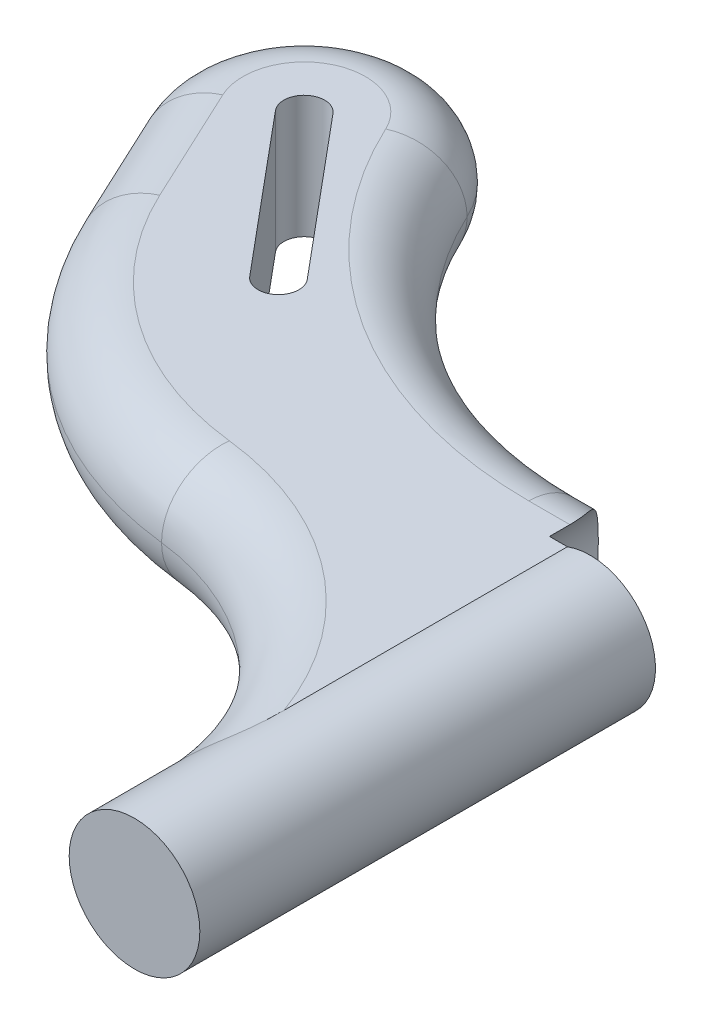
SolidWorks part; units mm, degrees
ref_plane "Front Plane" through (0, 0, 0) normal (0, 0, 1) x (1, 0, 0)
ref_plane "Top Plane" through (0, 0, 0) normal (0, 1, 0) x (1, 0, 0)
ref_plane "Right Plane" through (0, 0, 0) normal (1, 0, 0) x (0, 0, -1)
sketch "Sketch1" plane through (0, 0, 0) normal (0, 0, 1) x (1, 0, 0)
  circle A0 centre (0, 0) radius 8
  dimension "D1" = 16
extrude "Boss-Extrude1" add sketch "Sketch1" along normal blind 55.7812
sketch "Sketch2" plane through (0, 0, 0) normal (0, 1, 0) x (1, 0, 0)
  line L12 (0, 0) -> (0, -47.7812)
  line L13 (-71.8118, 9.1529) -> (-44.6353, 21.8588) construction
  line L14 (0, -47.7812) -> (-8, -47.7812)
  line L16 (-8, 0) -> (-8, -55.7812) construction
  line L17 (0, 0) -> (0, 10)
  line L22 (0, 10) -> (-10, 10)
  line L23 (-78.5882, 23.6471) -> (-71.8118, 9.1529)
  line L24 (-65, 30) -> (-65, 0) construction
  line L25 (-65, 0) -> (0, 0) construction
  line L26 (-51.4118, 36.3529) -> (0, -73.6111) construction
  line L28 (-8, -55.7812) -> (-8, -47.7812) construction
  line L30 (-65, 30) -> (-48.9689, 10.8166) construction
  line L32 (-66.9183, 28.3969) -> (-50.8872, 9.2135)
  line L35 (-47.0505, 12.4197) -> (-63.0817, 31.6031)
  line L36 (-48.9689, 10.8166) -> (0, -47.7812) construction
  arc A1 (-10, 10) -> (-51.4118, 36.3529) centre (-10, 55.7143) cw
  arc A3 (-51.4118, 36.3529) -> (-78.5882, 23.6471) centre (-65, 30) ccw
  arc A5 (-8, -47.7812) -> (-35.5631, -16.9075) centre (-39.0725, -47.7812) ccw
  arc A6 (-35.5631, -16.9075) -> (-71.8118, 9.1529) centre (-30.4, 28.5143) cw
  arc A7 (-63.0817, 31.6031) -> (-66.9183, 28.3969) centre (-65, 30) ccw
  arc A8 (-50.8872, 9.2135) -> (-47.0505, 12.4197) centre (-48.9689, 10.8166) ccw
  arc A9 (-50.572, 12.7349) -> (-50.8872, 9.2135) centre (-48.9689, 10.8166) ccw construction
  arc A10 (-63.3969, 28.0817) -> (-63.0817, 31.6031) centre (-65, 30) ccw construction
  arc A11 (-65, 27.5) -> (-63.3969, 28.0817) centre (-65, 30) ccw
  arc A12 (-66.9183, 28.3969) -> (-65, 27.5) centre (-65, 30) ccw construction
  arc A13 (-47.0505, 12.4197) -> (-50.572, 12.7349) centre (-48.9689, 10.8166) ccw construction
  point P21 (0, -45.9096)
  point P28 (0, -48.9344)
  dimension "D1" = 10
  dimension "D8" = 2.5
  dimension "D4" = 15
  dimension "D7" = 25
  dimension "D2" = 65
  dimension "D3" = 30
  dimension "D5" = 8
  dimension "D6" = 16
extrude "Boss-Extrude2" add sketch "Sketch2" along normal mid plane 15 contours A6 A5 L14 L12 L17 L22 A1 A3 L23 A8 L32 A7 L35 region at (-36.944, 0, -2.8474)
sketch "Sketch4" plane through (0, 0, 0) normal (0, 1, 0) x (1, 0, 0)
  line L0 (0, 0) -> (0, -55.7812) construction
  line L1 (-9, -70.7812) -> (0, -70.7812)
  line L2 (-9, -70.7812) -> (-9, -55.7812)
  line L3 (-9, -55.7812) -> (0, -55.7812)
  line L4 (0, -70.7812) -> (0, -55.7812)
  line L5 (-9, 0) -> (0, 0)
  line L6 (-9, 0) -> (-9, 15)
  line L7 (-9, 15) -> (0, 15)
  line L8 (0, 0) -> (0, 15)
  line L9 (-8, -55.7812) -> (8, -55.7812) construction
  point P7 (0, -57.3048)
  dimension "D1" = 15
  dimension "D2" = 9
revolve "Cut-Revolve1" cut sketch "Sketch4" angle 360 about L0
fillet "Fillet7" radius 7.5 12 edges at (-7.4875, -7.5, -10) (-34.5429, -7.5, -17.1469) (-71.3529, -7.5, -43.5882) (-75.2, -7.5, -16.4) (-57.085, -7.5, 8.6032) (-7.4875, 7.5, -10) (-34.5429, 7.5, -17.1469) (-71.3529, 7.5, -43.5882) (-75.2, 7.5, -16.4) (-57.085, 7.5, 8.6032) (-15.8933, -7.5, 27.0875) (-15.8933, 7.5, 27.0875)
